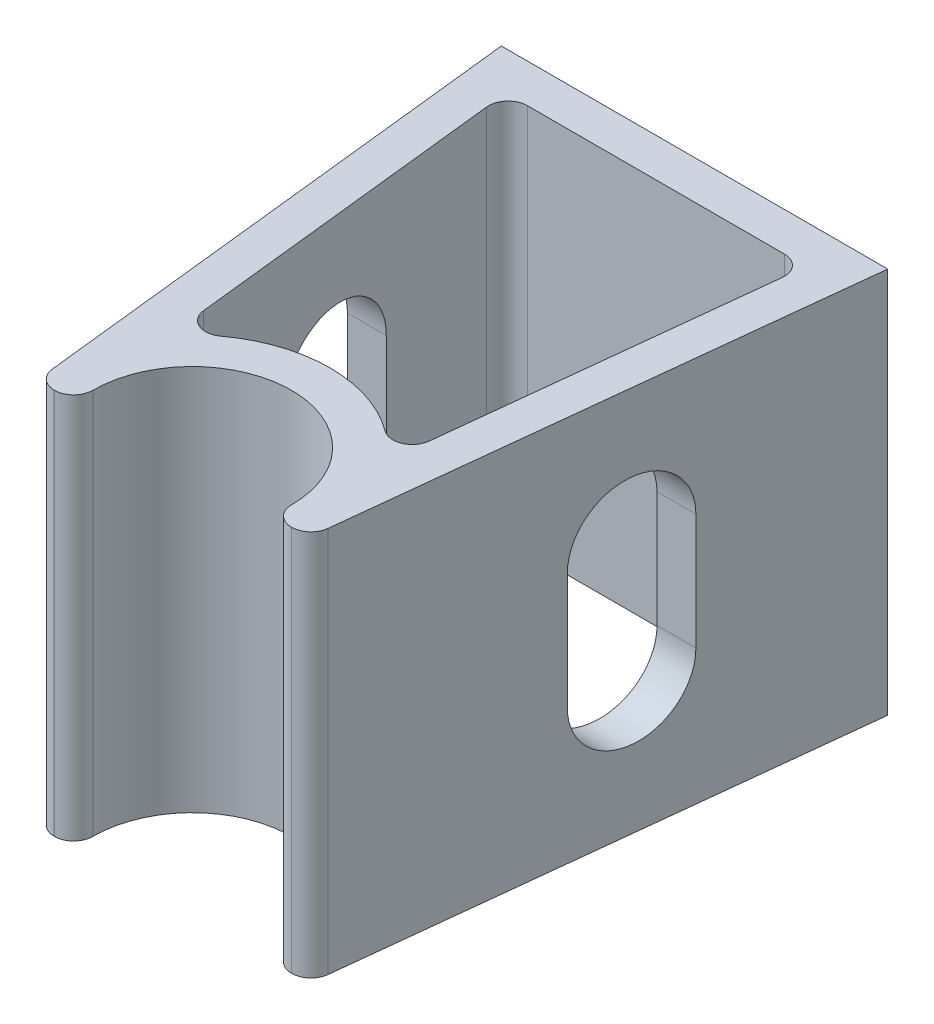
SolidWorks part; units mm, degrees
material "ABS"
ref_plane "Front Plane" through (0, 0, 0) normal (0, 0, 1) x (1, 0, 0)
ref_plane "Top Plane" through (0, 0, 0) normal (0, 1, 0) x (1, 0, 0)
ref_plane "Right Plane" through (0, 0, 0) normal (1, 0, 0) x (0, 0, -1)
sketch "Sketch1" plane through (0, 0, 0) normal (0, 1, 0) x (1, 0, 0)
  line L0 (-12.6, -2.5) -> (-17.6, -2.5)
  line L1 (-17.6, -2.5) -> (-25, 65)
  line L2 (-25, 65) -> (25, 65)
  line L3 (25, 65) -> (17.6, -2.5)
  line L4 (17.6, -2.5) -> (12.6, -2.5)
  arc A0 (12.6, -2.5) -> (-12.6, -2.5) centre (0, 0) ccw
  point P4 (0, 12.8456)
  dimension "D1" = 25.2
  dimension "D2" = 5
  dimension "D3" = 65
  dimension "D4" = 50
  dimension "D5" = 2.5
extrude "Boss-Extrude1" add sketch "Sketch1" along normal blind 50
sketch "Sketch2" plane through (0, 50, 0) normal (0, 1, 0) x (1, 0, 0)
  line L10 (14.0503, 11.0025) -> (19.4219, 60)
  line L11 (19.4219, 60) -> (-19.4219, 60)
  line L12 (-19.4219, 60) -> (-14.0503, 11.0025)
  line L13 (14.0503, 11.0025) -> (19.4219, 60)
  line L14 (19.4219, 60) -> (-19.4219, 60)
  line L15 (-19.4219, 60) -> (-14.0503, 11.0025)
  arc A2 (14.0503, 11.0025) -> (-14.0503, 11.0025) centre (0, 0) ccw
  arc A3 (14.0503, 11.0025) -> (-14.0503, 11.0025) centre (0, 0) ccw
  dimension "D1" = 5
extrude "Cut-Extrude1" cut sketch "Sketch2" against normal through all both and the other way through all
fillet "Fillet2" radius 2.5 8 edges at (-19.4219, 25, -60) (19.4219, 25, -60) (14.0503, 25, -11.0025) (-14.0503, 25, -11.0025) (17.6, 25, 2.5) (12.6, 25, 2.5) (-17.6, 25, 2.5) (-12.6, 25, 2.5)
sketch "Sketch3" plane through (0, 0, 0) normal (1, 0, 0) x (0, 0, -1)
  line L0 (35.1276, 0) -> (35.1276, 50) construction
  line L1 (-0.2724, 0) -> (65, 0) construction
  line L2 (-0.2724, 50) -> (65, 50) construction
  line L3 (35.1276, 32.5) -> (35.1276, 17.5) construction
  line L4 (42.6276, 32.5) -> (42.6276, 17.5)
  line L5 (27.6276, 32.5) -> (27.6276, 17.5)
  arc A1 (42.6276, 32.5) -> (27.6276, 32.5) centre (35.1276, 32.5) ccw
  arc A2 (27.6276, 17.5) -> (42.6276, 17.5) centre (35.1276, 17.5) ccw
  point P10 (35.1276, 25)
  dimension "D1" = 35.4
  dimension "D2" = 15
  dimension "D3" = 15
extrude "Cut-Extrude2" cut sketch "Sketch3" against normal through all both and the other way through all
sketch "Sketch4" plane through (0, 0, -65) normal (0, 0, -1) x (-1, 0, 0)
  text T0 "kawin"
extrude "Boss-Extrude2" add sketch "Sketch4" along normal blind 1
